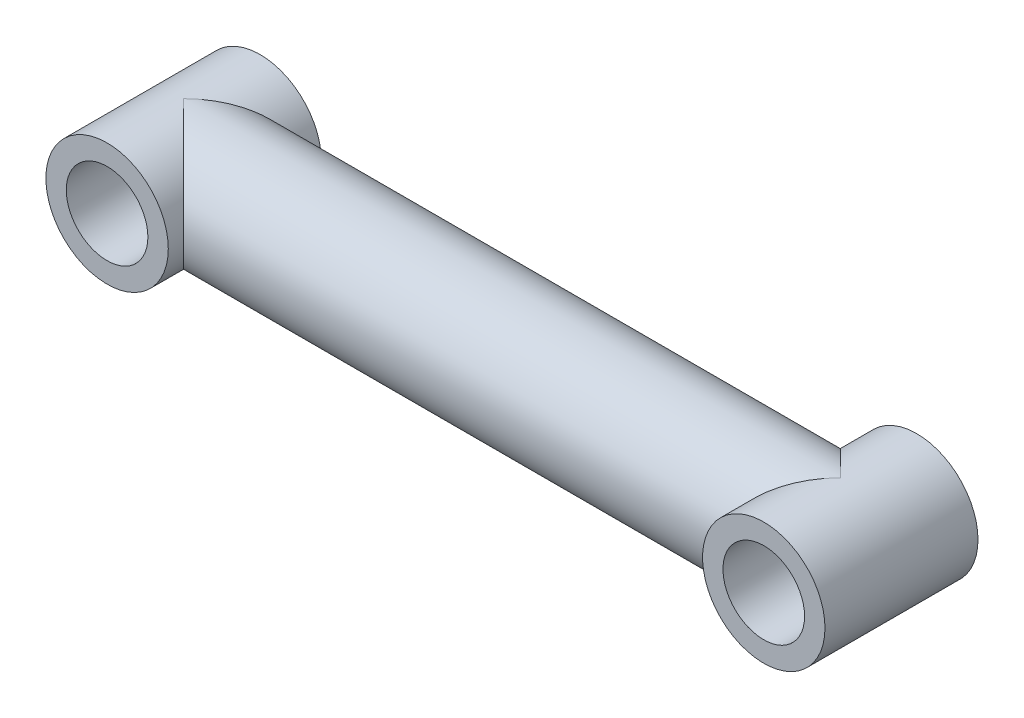
SolidWorks part; units mm, degrees
material "AISI 1035 Steel (SS)"
ref_plane "Front Plane" through (0, 0, 0) normal (0, 0, 1) x (1, 0, 0)
ref_plane "Top Plane" through (0, 0, 0) normal (0, 1, 0) x (1, 0, 0)
ref_plane "Right Plane" through (0, 0, 0) normal (1, 0, 0) x (0, 0, -1)
sketch "Sketch1" plane through (0, 0, 0) normal (1, 0, 0) x (0, 0, -1)
  circle A0 centre (0, 0) radius 4.8387
extrude "Boss-Extrude1" add sketch "Sketch1" along normal blind 25.9588 and the other way blind 25.9588
sketch "Sketch2" plane through (0, 0, 0) normal (0, 0, 1) x (1, 0, 0)
  line L0 (25.9588, -4.8387) -> (25.9588, 4.8387) construction
  line L1 (-25.9588, 4.8387) -> (-25.9588, -4.8387) construction
  circle A0 centre (25.9588, 0) radius 4.8387
  circle A3 centre (-25.9588, 0) radius 4.8387
extrude "Boss-Extrude2" add sketch "Sketch2" along normal blind 6.049 and the other way blind 6.049
sketch "Sketch3" plane through (0, 0, 6.049) normal (0, 0, 1) x (1, 0, 0)
  circle A0 centre (-25.9588, 0) radius 3.2258
  circle A1 centre (25.9588, 0) radius 3.2258
extrude "Cut-Extrude1" cut sketch "Sketch3" against normal through all
